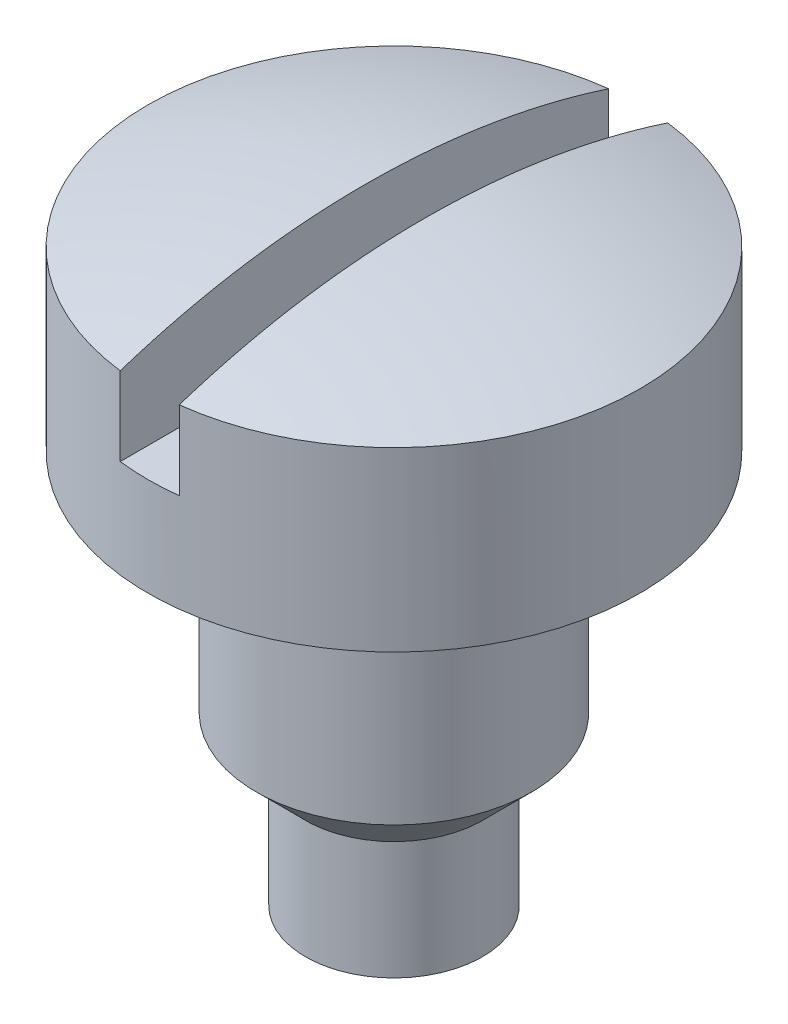
SolidWorks part; units mm, degrees
ref_plane "Front Plane" through (0, 0, 0) normal (0, 0, 1) x (1, 0, 0)
ref_plane "Top Plane" through (0, 0, 0) normal (0, 1, 0) x (1, 0, 0)
ref_plane "Right Plane" through (0, 0, 0) normal (1, 0, 0) x (0, 0, -1)
sketch "Sketch1" plane through (0, 0, 0) normal (0, 1, 0) x (1, 0, 0)
  circle A0 centre (0, 0) radius 1.25
  dimension "D1" = 2.5
extrude "Boss-Extrude1" add sketch "Sketch1" along normal blind 3.1
sketch "Sketch2" plane through (0, 0, 0) normal (0, 0, 1) x (1, 0, 0)
  line L0 (0, 0) -> (0, 3.1) construction
  line L1 (1.25, 3.1) -> (-1.25, 3.1) construction
  line L3 (1.25, 0) -> (1.25, 3.1) construction
  line L4 (1.25, 2.8997) -> (1.25, 3.3)
  line L6 (0, 3.1) -> (0, 3.3)
  line L7 (1.25, 3.3) -> (-1.25, 3.3)
  line L8 (1.25, 3.3) -> (0, 3.3)
  arc A0 (0, 3.1) -> (1.25, 2.8997) centre (0, -0.9) cw
  dimension "D1" = 0.2
  dimension "D2" = 4
revolve "Cut-Revolve1" cut sketch "Sketch2" angle 360 about L0
sketch "Sketch3" plane through (0, 0, 0) normal (0, -1, 0) x (1, 0, 0)
  circle A0 centre (0, 0) radius 0.7
  dimension "D1" = 1.4
extrude "Cut-Extrude1" cut sketch "Sketch3" against normal blind 2 flip side to cut
cosmetic thread "Cosmetic Thread1" parameters "D2"=1.057
sketch "Sketch4" plane through (0, 0, 0) normal (0, -1, 0) x (1, 0, 0)
  circle A0 centre (0, 0) radius 0.45
  dimension "D1" = 0.9
extrude "Cut-Extrude2" cut sketch "Sketch4" against normal blind 0.6 flip side to cut
chamfer "Chamfer1" distance 0.25 angle 45 1 edges at (0, 0.6, -0.7)
sketch "Sketch5" plane through (0, 0, 0) normal (0, 0, 1) x (1, 0, 0)
  line L0 (0, 0) -> (0, 3.1) construction
  line L1 (-0.45, 0) -> (0.45, 0) construction
  line L4 (-0.15, 3.0972) -> (-0.15, 2.5)
  line L5 (-0.15, 2.5) -> (0.15, 2.5)
  line L6 (0.15, 3.0972) -> (0.15, 2.5)
  arc A0 (1.25, 2.8997) -> (-1.25, 2.8997) centre (0, -0.9) ccw construction
  arc A1 (0.15, 3.0972) -> (-0.15, 3.0972) centre (0, -0.9) ccw
  dimension "D2" = 0.6
  dimension "D1" = 0.3
extrude "Cut-Extrude3" cut sketch "Sketch5" against normal through all both and the other way through all
